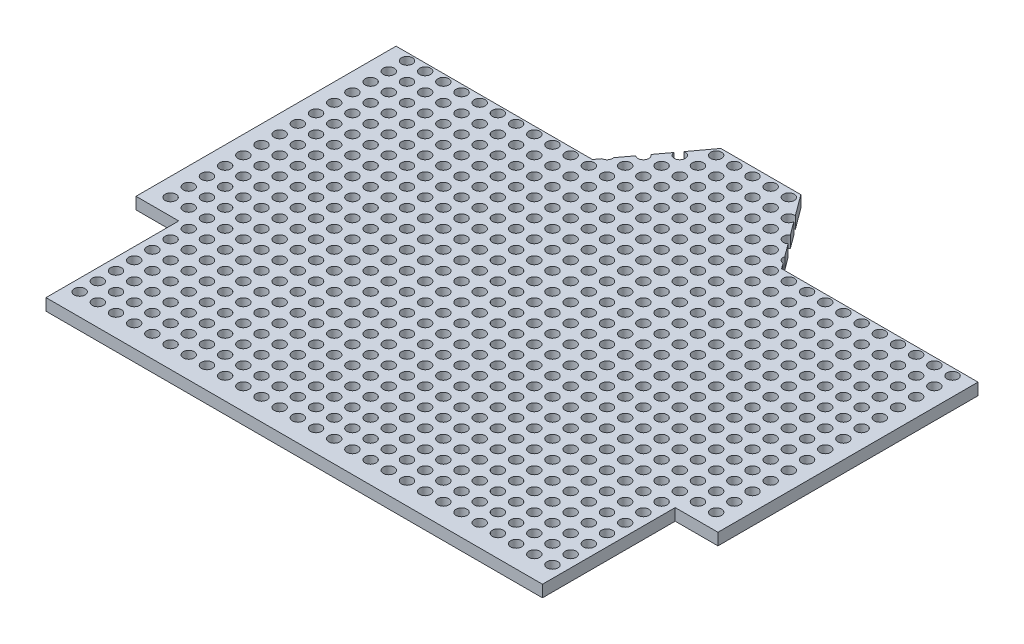
SolidWorks part; units mm, degrees
material "ABS"
ref_plane "Front Plane" through (0, 0, 0) normal (0, 0, 1) x (1, 0, 0)
ref_plane "Top Plane" through (0, 0, 0) normal (0, 1, 0) x (1, 0, 0)
ref_plane "Right Plane" through (0, 0, 0) normal (1, 0, 0) x (0, 0, -1)
sketch "Sketch1" plane through (0, 0, 0) normal (0, 1, 0) x (1, 0, 0)
  line L0 (-80, 35.75) -> (80, -35.75) construction
  line L1 (-11, 56.0362) -> (11, 56.0362)
  line L2 (-80, 35.75) -> (-80, -35.75)
  line L3 (-68.25, -72.25) -> (68.25, -72.25)
  line L4 (80, 35.75) -> (80, -35.75)
  line L5 (-80, -35.75) -> (-68.25, -35.75)
  line L6 (-68.25, -72.25) -> (-68.25, -35.75)
  line L7 (68.25, -72.25) -> (68.25, -35.75)
  line L8 (68.25, -35.75) -> (80, -35.75)
  line L9 (-80, 35.75) -> (-26, 35.75)
  line L10 (-26, 35.75) -> (-11, 56.0362)
  line L11 (11, 56.0362) -> (26, 35.75)
  line L12 (26, 35.75) -> (80, 35.75)
  line L13 (-75, 33.75) -> (-70, 33.75) construction
  line L14 (-75, 28.75) -> (-70, 28.75) construction
  circle A0 centre (-75, 33.75) radius 1.5025
  circle A1 centre (-70, 33.75) radius 1.5025
  circle A2 centre (-65, 33.75) radius 1.5025
  circle A3 centre (-60, 33.75) radius 1.5025
  circle A4 centre (-55, 33.75) radius 1.5025
  circle A5 centre (-50, 33.75) radius 1.5025
  circle A6 centre (-45, 33.75) radius 1.5025
  circle A7 centre (-40, 33.75) radius 1.5025
  circle A8 centre (-35, 33.75) radius 1.5025
  circle A9 centre (-30, 33.75) radius 1.5025
  circle A10 centre (-25, 33.75) radius 1.5025
  circle A11 centre (-20, 33.75) radius 1.5025
  circle A12 centre (-15, 33.75) radius 1.5025
  circle A13 centre (-10, 33.75) radius 1.5025
  circle A14 centre (-5, 33.75) radius 1.5025
  circle A15 centre (0, 33.75) radius 1.5025
  circle A16 centre (5, 33.75) radius 1.5025
  circle A17 centre (10, 33.75) radius 1.5025
  circle A18 centre (15, 33.75) radius 1.5025
  circle A19 centre (20, 33.75) radius 1.5025
  circle A20 centre (25, 33.75) radius 1.5025
  circle A21 centre (30, 33.75) radius 1.5025
  circle A22 centre (35, 33.75) radius 1.5025
  circle A23 centre (40, 33.75) radius 1.5025
  circle A24 centre (45, 33.75) radius 1.5025
  circle A25 centre (50, 33.75) radius 1.5025
  circle A26 centre (55, 33.75) radius 1.5025
  circle A27 centre (60, 33.75) radius 1.5025
  circle A28 centre (65, 33.75) radius 1.5025
  circle A29 centre (70, 33.75) radius 1.5025
  circle A30 centre (75, 33.75) radius 1.5025
  circle A31 centre (-75, 28.75) radius 1.5025
  arc A41 (-24.8897, 37.2516) -> (-23.535, 39.0837) centre (-25, 38.75) ccw
  circle A42 centre (-20, 38.75) radius 1.5025
  circle A43 centre (-15, 38.75) radius 1.5025
  circle A44 centre (-10, 38.75) radius 1.5025
  circle A45 centre (-5, 38.75) radius 1.5025
  circle A46 centre (0, 38.75) radius 1.5025
  circle A47 centre (5, 38.75) radius 1.5025
  circle A48 centre (10, 38.75) radius 1.5025
  circle A49 centre (15, 38.75) radius 1.5025
  circle A50 centre (20, 38.75) radius 1.5025
  arc A51 (23.535, 39.0837) -> (24.8897, 37.2516) centre (25, 38.75) ccw
  arc A72 (-20.9471, 42.5836) -> (-19.1623, 44.9973) centre (-20, 43.75) ccw
  circle A73 centre (-15, 43.75) radius 1.5025
  circle A74 centre (-10, 43.75) radius 1.5025
  circle A75 centre (-5, 43.75) radius 1.5025
  circle A76 centre (0, 43.75) radius 1.5025
  circle A77 centre (5, 43.75) radius 1.5025
  circle A78 centre (10, 43.75) radius 1.5025
  circle A79 centre (15, 43.75) radius 1.5025
  arc A80 (19.1623, 44.9973) -> (20.9471, 42.5836) centre (20, 43.75) ccw
  arc A103 (-16.4954, 48.6041) -> (-15.2987, 50.2225) centre (-15, 48.75) ccw
  circle A104 centre (-10, 48.75) radius 1.5025
  circle A105 centre (-5, 48.75) radius 1.5025
  circle A106 centre (0, 48.75) radius 1.5025
  circle A107 centre (5, 48.75) radius 1.5025
  circle A108 centre (10, 48.75) radius 1.5025
  arc A109 (15.2987, 50.2225) -> (16.4954, 48.6041) centre (15, 48.75) ccw
  circle A134 centre (-10, 53.75) radius 1.5025
  circle A135 centre (-5, 53.75) radius 1.5025
  circle A136 centre (0, 53.75) radius 1.5025
  circle A137 centre (5, 53.75) radius 1.5025
  circle A138 centre (10, 53.75) radius 1.5025
  circle A152 centre (-75, 38.75) radius 1.5025
  circle A156 centre (-70, 28.75) radius 1.5025
  circle A157 centre (-65, 28.75) radius 1.5025
  circle A158 centre (-60, 28.75) radius 1.5025
  circle A159 centre (-55, 28.75) radius 1.5025
  circle A160 centre (-50, 28.75) radius 1.5025
  circle A161 centre (-45, 28.75) radius 1.5025
  circle A162 centre (-40, 28.75) radius 1.5025
  circle A163 centre (-35, 28.75) radius 1.5025
  circle A164 centre (-30, 28.75) radius 1.5025
  circle A165 centre (-25, 28.75) radius 1.5025
  circle A166 centre (-20, 28.75) radius 1.5025
  circle A167 centre (-15, 28.75) radius 1.5025
  circle A168 centre (-10, 28.75) radius 1.5025
  circle A169 centre (-5, 28.75) radius 1.5025
  circle A170 centre (0, 28.75) radius 1.5025
  circle A171 centre (5, 28.75) radius 1.5025
  circle A172 centre (10, 28.75) radius 1.5025
  circle A173 centre (15, 28.75) radius 1.5025
  circle A174 centre (20, 28.75) radius 1.5025
  circle A175 centre (25, 28.75) radius 1.5025
  circle A176 centre (30, 28.75) radius 1.5025
  circle A177 centre (35, 28.75) radius 1.5025
  circle A178 centre (40, 28.75) radius 1.5025
  circle A179 centre (45, 28.75) radius 1.5025
  circle A180 centre (50, 28.75) radius 1.5025
  circle A181 centre (55, 28.75) radius 1.5025
  circle A182 centre (60, 28.75) radius 1.5025
  circle A183 centre (65, 28.75) radius 1.5025
  circle A184 centre (70, 28.75) radius 1.5025
  circle A185 centre (75, 28.75) radius 1.5025
  circle A186 centre (-70, 23.75) radius 1.5025
  circle A187 centre (-65, 23.75) radius 1.5025
  circle A188 centre (-60, 23.75) radius 1.5025
  circle A189 centre (-55, 23.75) radius 1.5025
  circle A190 centre (-50, 23.75) radius 1.5025
  circle A191 centre (-45, 23.75) radius 1.5025
  circle A192 centre (-40, 23.75) radius 1.5025
  circle A193 centre (-35, 23.75) radius 1.5025
  circle A194 centre (-30, 23.75) radius 1.5025
  circle A195 centre (-25, 23.75) radius 1.5025
  circle A196 centre (-20, 23.75) radius 1.5025
  circle A197 centre (-15, 23.75) radius 1.5025
  circle A198 centre (-10, 23.75) radius 1.5025
  circle A199 centre (-5, 23.75) radius 1.5025
  circle A200 centre (0, 23.75) radius 1.5025
  circle A201 centre (5, 23.75) radius 1.5025
  circle A202 centre (10, 23.75) radius 1.5025
  circle A203 centre (15, 23.75) radius 1.5025
  circle A204 centre (20, 23.75) radius 1.5025
  circle A205 centre (25, 23.75) radius 1.5025
  circle A206 centre (30, 23.75) radius 1.5025
  circle A207 centre (35, 23.75) radius 1.5025
  circle A208 centre (40, 23.75) radius 1.5025
  circle A209 centre (45, 23.75) radius 1.5025
  circle A210 centre (50, 23.75) radius 1.5025
  circle A211 centre (55, 23.75) radius 1.5025
  circle A212 centre (60, 23.75) radius 1.5025
  circle A213 centre (65, 23.75) radius 1.5025
  circle A214 centre (70, 23.75) radius 1.5025
  circle A215 centre (75, 23.75) radius 1.5025
  circle A216 centre (-70, 18.75) radius 1.5025
  circle A217 centre (-65, 18.75) radius 1.5025
  circle A218 centre (-60, 18.75) radius 1.5025
  circle A219 centre (-55, 18.75) radius 1.5025
  circle A220 centre (-50, 18.75) radius 1.5025
  circle A221 centre (-45, 18.75) radius 1.5025
  circle A222 centre (-40, 18.75) radius 1.5025
  circle A223 centre (-35, 18.75) radius 1.5025
  circle A224 centre (-30, 18.75) radius 1.5025
  circle A225 centre (-25, 18.75) radius 1.5025
  circle A226 centre (-20, 18.75) radius 1.5025
  circle A227 centre (-15, 18.75) radius 1.5025
  circle A228 centre (-10, 18.75) radius 1.5025
  circle A229 centre (-5, 18.75) radius 1.5025
  circle A230 centre (0, 18.75) radius 1.5025
  circle A231 centre (5, 18.75) radius 1.5025
  circle A232 centre (10, 18.75) radius 1.5025
  circle A233 centre (15, 18.75) radius 1.5025
  circle A234 centre (20, 18.75) radius 1.5025
  circle A235 centre (25, 18.75) radius 1.5025
  circle A236 centre (30, 18.75) radius 1.5025
  circle A237 centre (35, 18.75) radius 1.5025
  circle A238 centre (40, 18.75) radius 1.5025
  circle A239 centre (45, 18.75) radius 1.5025
  circle A240 centre (50, 18.75) radius 1.5025
  circle A241 centre (55, 18.75) radius 1.5025
  circle A242 centre (60, 18.75) radius 1.5025
  circle A243 centre (65, 18.75) radius 1.5025
  circle A244 centre (70, 18.75) radius 1.5025
  circle A245 centre (75, 18.75) radius 1.5025
  circle A246 centre (-70, 13.75) radius 1.5025
  circle A247 centre (-65, 13.75) radius 1.5025
  circle A248 centre (-60, 13.75) radius 1.5025
  circle A249 centre (-55, 13.75) radius 1.5025
  circle A250 centre (-50, 13.75) radius 1.5025
  circle A251 centre (-45, 13.75) radius 1.5025
  circle A252 centre (-40, 13.75) radius 1.5025
  circle A253 centre (-35, 13.75) radius 1.5025
  circle A254 centre (-30, 13.75) radius 1.5025
  circle A255 centre (-25, 13.75) radius 1.5025
  circle A256 centre (-20, 13.75) radius 1.5025
  circle A257 centre (-15, 13.75) radius 1.5025
  circle A258 centre (-10, 13.75) radius 1.5025
  circle A259 centre (-5, 13.75) radius 1.5025
  circle A260 centre (0, 13.75) radius 1.5025
  circle A261 centre (5, 13.75) radius 1.5025
  circle A262 centre (10, 13.75) radius 1.5025
  circle A263 centre (15, 13.75) radius 1.5025
  circle A264 centre (20, 13.75) radius 1.5025
  circle A265 centre (25, 13.75) radius 1.5025
  circle A266 centre (30, 13.75) radius 1.5025
  circle A267 centre (35, 13.75) radius 1.5025
  circle A268 centre (40, 13.75) radius 1.5025
  circle A269 centre (45, 13.75) radius 1.5025
  circle A270 centre (50, 13.75) radius 1.5025
  circle A271 centre (55, 13.75) radius 1.5025
  circle A272 centre (60, 13.75) radius 1.5025
  circle A273 centre (65, 13.75) radius 1.5025
  circle A274 centre (70, 13.75) radius 1.5025
  circle A275 centre (75, 13.75) radius 1.5025
  circle A276 centre (-70, 8.75) radius 1.5025
  circle A277 centre (-65, 8.75) radius 1.5025
  circle A278 centre (-60, 8.75) radius 1.5025
  circle A279 centre (-55, 8.75) radius 1.5025
  circle A280 centre (-50, 8.75) radius 1.5025
  circle A281 centre (-45, 8.75) radius 1.5025
  circle A282 centre (-40, 8.75) radius 1.5025
  circle A283 centre (-35, 8.75) radius 1.5025
  circle A284 centre (-30, 8.75) radius 1.5025
  circle A285 centre (-25, 8.75) radius 1.5025
  circle A286 centre (-20, 8.75) radius 1.5025
  circle A287 centre (-15, 8.75) radius 1.5025
  circle A288 centre (-10, 8.75) radius 1.5025
  circle A289 centre (-5, 8.75) radius 1.5025
  circle A290 centre (0, 8.75) radius 1.5025
  circle A291 centre (5, 8.75) radius 1.5025
  circle A292 centre (10, 8.75) radius 1.5025
  circle A293 centre (15, 8.75) radius 1.5025
  circle A294 centre (20, 8.75) radius 1.5025
  circle A295 centre (25, 8.75) radius 1.5025
  circle A296 centre (30, 8.75) radius 1.5025
  circle A297 centre (35, 8.75) radius 1.5025
  circle A298 centre (40, 8.75) radius 1.5025
  circle A299 centre (45, 8.75) radius 1.5025
  circle A300 centre (50, 8.75) radius 1.5025
  circle A301 centre (55, 8.75) radius 1.5025
  circle A302 centre (60, 8.75) radius 1.5025
  circle A303 centre (65, 8.75) radius 1.5025
  circle A304 centre (70, 8.75) radius 1.5025
  circle A305 centre (75, 8.75) radius 1.5025
  circle A306 centre (-70, 3.75) radius 1.5025
  circle A307 centre (-65, 3.75) radius 1.5025
  circle A308 centre (-60, 3.75) radius 1.5025
  circle A309 centre (-55, 3.75) radius 1.5025
  circle A310 centre (-50, 3.75) radius 1.5025
  circle A311 centre (-45, 3.75) radius 1.5025
  circle A312 centre (-40, 3.75) radius 1.5025
  circle A313 centre (-35, 3.75) radius 1.5025
  circle A314 centre (-30, 3.75) radius 1.5025
  circle A315 centre (-25, 3.75) radius 1.5025
  circle A316 centre (-20, 3.75) radius 1.5025
  circle A317 centre (-15, 3.75) radius 1.5025
  circle A318 centre (-10, 3.75) radius 1.5025
  circle A319 centre (-5, 3.75) radius 1.5025
  circle A320 centre (0, 3.75) radius 1.5025
  circle A321 centre (5, 3.75) radius 1.5025
  circle A322 centre (10, 3.75) radius 1.5025
  circle A323 centre (15, 3.75) radius 1.5025
  circle A324 centre (20, 3.75) radius 1.5025
  circle A325 centre (25, 3.75) radius 1.5025
  circle A326 centre (30, 3.75) radius 1.5025
  circle A327 centre (35, 3.75) radius 1.5025
  circle A328 centre (40, 3.75) radius 1.5025
  circle A329 centre (45, 3.75) radius 1.5025
  circle A330 centre (50, 3.75) radius 1.5025
  circle A331 centre (55, 3.75) radius 1.5025
  circle A332 centre (60, 3.75) radius 1.5025
  circle A333 centre (65, 3.75) radius 1.5025
  circle A334 centre (70, 3.75) radius 1.5025
  circle A335 centre (75, 3.75) radius 1.5025
  circle A336 centre (-70, -1.25) radius 1.5025
  circle A337 centre (-65, -1.25) radius 1.5025
  circle A338 centre (-60, -1.25) radius 1.5025
  circle A339 centre (-55, -1.25) radius 1.5025
  circle A340 centre (-50, -1.25) radius 1.5025
  circle A341 centre (-45, -1.25) radius 1.5025
  circle A342 centre (-40, -1.25) radius 1.5025
  circle A343 centre (-35, -1.25) radius 1.5025
  circle A344 centre (-30, -1.25) radius 1.5025
  circle A345 centre (-25, -1.25) radius 1.5025
  circle A346 centre (-20, -1.25) radius 1.5025
  circle A347 centre (-15, -1.25) radius 1.5025
  circle A348 centre (-10, -1.25) radius 1.5025
  circle A349 centre (-5, -1.25) radius 1.5025
  circle A350 centre (0, -1.25) radius 1.5025
  circle A351 centre (5, -1.25) radius 1.5025
  circle A352 centre (10, -1.25) radius 1.5025
  circle A353 centre (15, -1.25) radius 1.5025
  circle A354 centre (20, -1.25) radius 1.5025
  circle A355 centre (25, -1.25) radius 1.5025
  circle A356 centre (30, -1.25) radius 1.5025
  circle A357 centre (35, -1.25) radius 1.5025
  circle A358 centre (40, -1.25) radius 1.5025
  circle A359 centre (45, -1.25) radius 1.5025
  circle A360 centre (50, -1.25) radius 1.5025
  circle A361 centre (55, -1.25) radius 1.5025
  circle A362 centre (60, -1.25) radius 1.5025
  circle A363 centre (65, -1.25) radius 1.5025
  circle A364 centre (70, -1.25) radius 1.5025
  circle A365 centre (75, -1.25) radius 1.5025
  circle A366 centre (-70, -6.25) radius 1.5025
  circle A367 centre (-65, -6.25) radius 1.5025
  circle A368 centre (-60, -6.25) radius 1.5025
  circle A369 centre (-55, -6.25) radius 1.5025
  circle A370 centre (-50, -6.25) radius 1.5025
  circle A371 centre (-45, -6.25) radius 1.5025
  circle A372 centre (-40, -6.25) radius 1.5025
  circle A373 centre (-35, -6.25) radius 1.5025
  circle A374 centre (-30, -6.25) radius 1.5025
  circle A375 centre (-25, -6.25) radius 1.5025
  circle A376 centre (-20, -6.25) radius 1.5025
  circle A377 centre (-15, -6.25) radius 1.5025
  circle A378 centre (-10, -6.25) radius 1.5025
  circle A379 centre (-5, -6.25) radius 1.5025
  circle A380 centre (0, -6.25) radius 1.5025
  circle A381 centre (5, -6.25) radius 1.5025
  circle A382 centre (10, -6.25) radius 1.5025
  circle A383 centre (15, -6.25) radius 1.5025
  circle A384 centre (20, -6.25) radius 1.5025
  circle A385 centre (25, -6.25) radius 1.5025
  circle A386 centre (30, -6.25) radius 1.5025
  circle A387 centre (35, -6.25) radius 1.5025
  circle A388 centre (40, -6.25) radius 1.5025
  circle A389 centre (45, -6.25) radius 1.5025
  circle A390 centre (50, -6.25) radius 1.5025
  circle A391 centre (55, -6.25) radius 1.5025
  circle A392 centre (60, -6.25) radius 1.5025
  circle A393 centre (65, -6.25) radius 1.5025
  circle A394 centre (70, -6.25) radius 1.5025
  circle A395 centre (75, -6.25) radius 1.5025
  circle A396 centre (-70, -11.25) radius 1.5025
  circle A397 centre (-65, -11.25) radius 1.5025
  circle A398 centre (-60, -11.25) radius 1.5025
  circle A399 centre (-55, -11.25) radius 1.5025
  circle A400 centre (-50, -11.25) radius 1.5025
  circle A401 centre (-45, -11.25) radius 1.5025
  circle A402 centre (-40, -11.25) radius 1.5025
  circle A403 centre (-35, -11.25) radius 1.5025
  circle A404 centre (-30, -11.25) radius 1.5025
  circle A405 centre (-25, -11.25) radius 1.5025
  circle A406 centre (-20, -11.25) radius 1.5025
  circle A407 centre (-15, -11.25) radius 1.5025
  circle A408 centre (-10, -11.25) radius 1.5025
  circle A409 centre (-5, -11.25) radius 1.5025
  circle A410 centre (0, -11.25) radius 1.5025
  circle A411 centre (5, -11.25) radius 1.5025
  circle A412 centre (10, -11.25) radius 1.5025
  circle A413 centre (15, -11.25) radius 1.5025
  circle A414 centre (20, -11.25) radius 1.5025
  circle A415 centre (25, -11.25) radius 1.5025
  circle A416 centre (30, -11.25) radius 1.5025
  circle A417 centre (35, -11.25) radius 1.5025
  circle A418 centre (40, -11.25) radius 1.5025
  circle A419 centre (45, -11.25) radius 1.5025
  circle A420 centre (50, -11.25) radius 1.5025
  circle A421 centre (55, -11.25) radius 1.5025
  circle A422 centre (60, -11.25) radius 1.5025
  circle A423 centre (65, -11.25) radius 1.5025
  circle A424 centre (70, -11.25) radius 1.5025
  circle A425 centre (75, -11.25) radius 1.5025
  circle A426 centre (-70, -16.25) radius 1.5025
  circle A427 centre (-65, -16.25) radius 1.5025
  circle A428 centre (-60, -16.25) radius 1.5025
  circle A429 centre (-55, -16.25) radius 1.5025
  circle A430 centre (-50, -16.25) radius 1.5025
  circle A431 centre (-45, -16.25) radius 1.5025
  circle A432 centre (-40, -16.25) radius 1.5025
  circle A433 centre (-35, -16.25) radius 1.5025
  circle A434 centre (-30, -16.25) radius 1.5025
  circle A435 centre (-25, -16.25) radius 1.5025
  circle A436 centre (-20, -16.25) radius 1.5025
  circle A437 centre (-15, -16.25) radius 1.5025
  circle A438 centre (-10, -16.25) radius 1.5025
  circle A439 centre (-5, -16.25) radius 1.5025
  circle A440 centre (0, -16.25) radius 1.5025
  circle A441 centre (5, -16.25) radius 1.5025
  circle A442 centre (10, -16.25) radius 1.5025
  circle A443 centre (15, -16.25) radius 1.5025
  circle A444 centre (20, -16.25) radius 1.5025
  circle A445 centre (25, -16.25) radius 1.5025
  circle A446 centre (30, -16.25) radius 1.5025
  circle A447 centre (35, -16.25) radius 1.5025
  circle A448 centre (40, -16.25) radius 1.5025
  circle A449 centre (45, -16.25) radius 1.5025
  circle A450 centre (50, -16.25) radius 1.5025
  circle A451 centre (55, -16.25) radius 1.5025
  circle A452 centre (60, -16.25) radius 1.5025
  circle A453 centre (65, -16.25) radius 1.5025
  circle A454 centre (70, -16.25) radius 1.5025
  circle A455 centre (75, -16.25) radius 1.5025
  circle A456 centre (-70, -21.25) radius 1.5025
  circle A457 centre (-65, -21.25) radius 1.5025
  circle A458 centre (-60, -21.25) radius 1.5025
  circle A459 centre (-55, -21.25) radius 1.5025
  circle A460 centre (-50, -21.25) radius 1.5025
  circle A461 centre (-45, -21.25) radius 1.5025
  circle A462 centre (-40, -21.25) radius 1.5025
  circle A463 centre (-35, -21.25) radius 1.5025
  circle A464 centre (-30, -21.25) radius 1.5025
  circle A465 centre (-25, -21.25) radius 1.5025
  circle A466 centre (-20, -21.25) radius 1.5025
  circle A467 centre (-15, -21.25) radius 1.5025
  circle A468 centre (-10, -21.25) radius 1.5025
  circle A469 centre (-5, -21.25) radius 1.5025
  circle A470 centre (0, -21.25) radius 1.5025
  circle A471 centre (5, -21.25) radius 1.5025
  circle A472 centre (10, -21.25) radius 1.5025
  circle A473 centre (15, -21.25) radius 1.5025
  circle A474 centre (20, -21.25) radius 1.5025
  circle A475 centre (25, -21.25) radius 1.5025
  circle A476 centre (30, -21.25) radius 1.5025
  circle A477 centre (35, -21.25) radius 1.5025
  circle A478 centre (40, -21.25) radius 1.5025
  circle A479 centre (45, -21.25) radius 1.5025
  circle A480 centre (50, -21.25) radius 1.5025
  circle A481 centre (55, -21.25) radius 1.5025
  circle A482 centre (60, -21.25) radius 1.5025
  circle A483 centre (65, -21.25) radius 1.5025
  circle A484 centre (70, -21.25) radius 1.5025
  circle A485 centre (75, -21.25) radius 1.5025
  circle A486 centre (-70, -26.25) radius 1.5025
  circle A487 centre (-65, -26.25) radius 1.5025
  circle A488 centre (-60, -26.25) radius 1.5025
  circle A489 centre (-55, -26.25) radius 1.5025
  circle A490 centre (-50, -26.25) radius 1.5025
  circle A491 centre (-45, -26.25) radius 1.5025
  circle A492 centre (-40, -26.25) radius 1.5025
  circle A493 centre (-35, -26.25) radius 1.5025
  circle A494 centre (-30, -26.25) radius 1.5025
  circle A495 centre (-25, -26.25) radius 1.5025
  circle A496 centre (-20, -26.25) radius 1.5025
  circle A497 centre (-15, -26.25) radius 1.5025
  circle A498 centre (-10, -26.25) radius 1.5025
  circle A499 centre (-5, -26.25) radius 1.5025
  circle A500 centre (0, -26.25) radius 1.5025
  circle A501 centre (5, -26.25) radius 1.5025
  circle A502 centre (10, -26.25) radius 1.5025
  circle A503 centre (15, -26.25) radius 1.5025
  circle A504 centre (20, -26.25) radius 1.5025
  circle A505 centre (25, -26.25) radius 1.5025
  circle A506 centre (30, -26.25) radius 1.5025
  circle A507 centre (35, -26.25) radius 1.5025
  circle A508 centre (40, -26.25) radius 1.5025
  circle A509 centre (45, -26.25) radius 1.5025
  circle A510 centre (50, -26.25) radius 1.5025
  circle A511 centre (55, -26.25) radius 1.5025
  circle A512 centre (60, -26.25) radius 1.5025
  circle A513 centre (65, -26.25) radius 1.5025
  circle A514 centre (70, -26.25) radius 1.5025
  circle A515 centre (75, -26.25) radius 1.5025
  circle A516 centre (-70, -31.25) radius 1.5025
  circle A517 centre (-65, -31.25) radius 1.5025
  circle A518 centre (-60, -31.25) radius 1.5025
  circle A519 centre (-55, -31.25) radius 1.5025
  circle A520 centre (-50, -31.25) radius 1.5025
  circle A521 centre (-45, -31.25) radius 1.5025
  circle A522 centre (-40, -31.25) radius 1.5025
  circle A523 centre (-35, -31.25) radius 1.5025
  circle A524 centre (-30, -31.25) radius 1.5025
  circle A525 centre (-25, -31.25) radius 1.5025
  circle A526 centre (-20, -31.25) radius 1.5025
  circle A527 centre (-15, -31.25) radius 1.5025
  circle A528 centre (-10, -31.25) radius 1.5025
  circle A529 centre (-5, -31.25) radius 1.5025
  circle A530 centre (0, -31.25) radius 1.5025
  circle A531 centre (5, -31.25) radius 1.5025
  circle A532 centre (10, -31.25) radius 1.5025
  circle A533 centre (15, -31.25) radius 1.5025
  circle A534 centre (20, -31.25) radius 1.5025
  circle A535 centre (25, -31.25) radius 1.5025
  circle A536 centre (30, -31.25) radius 1.5025
  circle A537 centre (35, -31.25) radius 1.5025
  circle A538 centre (40, -31.25) radius 1.5025
  circle A539 centre (45, -31.25) radius 1.5025
  circle A540 centre (50, -31.25) radius 1.5025
  circle A541 centre (55, -31.25) radius 1.5025
  circle A542 centre (60, -31.25) radius 1.5025
  circle A543 centre (65, -31.25) radius 1.5025
  circle A544 centre (70, -31.25) radius 1.5025
  circle A545 centre (75, -31.25) radius 1.5025
  circle A547 centre (-65, -36.25) radius 1.5025
  circle A548 centre (-60, -36.25) radius 1.5025
  circle A549 centre (-55, -36.25) radius 1.5025
  circle A550 centre (-50, -36.25) radius 1.5025
  circle A551 centre (-45, -36.25) radius 1.5025
  circle A552 centre (-40, -36.25) radius 1.5025
  circle A553 centre (-35, -36.25) radius 1.5025
  circle A554 centre (-30, -36.25) radius 1.5025
  circle A555 centre (-25, -36.25) radius 1.5025
  circle A556 centre (-20, -36.25) radius 1.5025
  circle A557 centre (-15, -36.25) radius 1.5025
  circle A558 centre (-10, -36.25) radius 1.5025
  circle A559 centre (-5, -36.25) radius 1.5025
  circle A560 centre (0, -36.25) radius 1.5025
  circle A561 centre (5, -36.25) radius 1.5025
  circle A562 centre (10, -36.25) radius 1.5025
  circle A563 centre (15, -36.25) radius 1.5025
  circle A564 centre (20, -36.25) radius 1.5025
  circle A565 centre (25, -36.25) radius 1.5025
  circle A566 centre (30, -36.25) radius 1.5025
  circle A567 centre (35, -36.25) radius 1.5025
  circle A568 centre (40, -36.25) radius 1.5025
  circle A569 centre (45, -36.25) radius 1.5025
  circle A570 centre (50, -36.25) radius 1.5025
  circle A571 centre (55, -36.25) radius 1.5025
  circle A572 centre (60, -36.25) radius 1.5025
  circle A573 centre (65, -36.25) radius 1.5025
  circle A577 centre (-65, -41.25) radius 1.5025
  circle A578 centre (-60, -41.25) radius 1.5025
  circle A579 centre (-55, -41.25) radius 1.5025
  circle A580 centre (-50, -41.25) radius 1.5025
  circle A581 centre (-45, -41.25) radius 1.5025
  circle A582 centre (-40, -41.25) radius 1.5025
  circle A583 centre (-35, -41.25) radius 1.5025
  circle A584 centre (-30, -41.25) radius 1.5025
  circle A585 centre (-25, -41.25) radius 1.5025
  circle A586 centre (-20, -41.25) radius 1.5025
  circle A587 centre (-15, -41.25) radius 1.5025
  circle A588 centre (-10, -41.25) radius 1.5025
  circle A589 centre (-5, -41.25) radius 1.5025
  circle A590 centre (0, -41.25) radius 1.5025
  circle A591 centre (5, -41.25) radius 1.5025
  circle A592 centre (10, -41.25) radius 1.5025
  circle A593 centre (15, -41.25) radius 1.5025
  circle A594 centre (20, -41.25) radius 1.5025
  circle A595 centre (25, -41.25) radius 1.5025
  circle A596 centre (30, -41.25) radius 1.5025
  circle A597 centre (35, -41.25) radius 1.5025
  circle A598 centre (40, -41.25) radius 1.5025
  circle A599 centre (45, -41.25) radius 1.5025
  circle A600 centre (50, -41.25) radius 1.5025
  circle A601 centre (55, -41.25) radius 1.5025
  circle A602 centre (60, -41.25) radius 1.5025
  circle A603 centre (65, -41.25) radius 1.5025
  circle A607 centre (-65, -46.25) radius 1.5025
  circle A608 centre (-60, -46.25) radius 1.5025
  circle A609 centre (-55, -46.25) radius 1.5025
  circle A610 centre (-50, -46.25) radius 1.5025
  circle A611 centre (-45, -46.25) radius 1.5025
  circle A612 centre (-40, -46.25) radius 1.5025
  circle A613 centre (-35, -46.25) radius 1.5025
  circle A614 centre (-30, -46.25) radius 1.5025
  circle A615 centre (-25, -46.25) radius 1.5025
  circle A616 centre (-20, -46.25) radius 1.5025
  circle A617 centre (-15, -46.25) radius 1.5025
  circle A618 centre (-10, -46.25) radius 1.5025
  circle A619 centre (-5, -46.25) radius 1.5025
  circle A620 centre (0, -46.25) radius 1.5025
  circle A621 centre (5, -46.25) radius 1.5025
  circle A622 centre (10, -46.25) radius 1.5025
  circle A623 centre (15, -46.25) radius 1.5025
  circle A624 centre (20, -46.25) radius 1.5025
  circle A625 centre (25, -46.25) radius 1.5025
  circle A626 centre (30, -46.25) radius 1.5025
  circle A627 centre (35, -46.25) radius 1.5025
  circle A628 centre (40, -46.25) radius 1.5025
  circle A629 centre (45, -46.25) radius 1.5025
  circle A630 centre (50, -46.25) radius 1.5025
  circle A631 centre (55, -46.25) radius 1.5025
  circle A632 centre (60, -46.25) radius 1.5025
  circle A633 centre (65, -46.25) radius 1.5025
  circle A637 centre (-65, -51.25) radius 1.5025
  circle A638 centre (-60, -51.25) radius 1.5025
  circle A639 centre (-55, -51.25) radius 1.5025
  circle A640 centre (-50, -51.25) radius 1.5025
  circle A641 centre (-45, -51.25) radius 1.5025
  circle A642 centre (-40, -51.25) radius 1.5025
  circle A643 centre (-35, -51.25) radius 1.5025
  circle A644 centre (-30, -51.25) radius 1.5025
  circle A645 centre (-25, -51.25) radius 1.5025
  circle A646 centre (-20, -51.25) radius 1.5025
  circle A647 centre (-15, -51.25) radius 1.5025
  circle A648 centre (-10, -51.25) radius 1.5025
  circle A649 centre (-5, -51.25) radius 1.5025
  circle A650 centre (0, -51.25) radius 1.5025
  circle A651 centre (5, -51.25) radius 1.5025
  circle A652 centre (10, -51.25) radius 1.5025
  circle A653 centre (15, -51.25) radius 1.5025
  circle A654 centre (20, -51.25) radius 1.5025
  circle A655 centre (25, -51.25) radius 1.5025
  circle A656 centre (30, -51.25) radius 1.5025
  circle A657 centre (35, -51.25) radius 1.5025
  circle A658 centre (40, -51.25) radius 1.5025
  circle A659 centre (45, -51.25) radius 1.5025
  circle A660 centre (50, -51.25) radius 1.5025
  circle A661 centre (55, -51.25) radius 1.5025
  circle A662 centre (60, -51.25) radius 1.5025
  circle A663 centre (65, -51.25) radius 1.5025
  circle A667 centre (-65, -56.25) radius 1.5025
  circle A668 centre (-60, -56.25) radius 1.5025
  circle A669 centre (-55, -56.25) radius 1.5025
  circle A670 centre (-50, -56.25) radius 1.5025
  circle A671 centre (-45, -56.25) radius 1.5025
  circle A672 centre (-40, -56.25) radius 1.5025
  circle A673 centre (-35, -56.25) radius 1.5025
  circle A674 centre (-30, -56.25) radius 1.5025
  circle A675 centre (-25, -56.25) radius 1.5025
  circle A676 centre (-20, -56.25) radius 1.5025
  circle A677 centre (-15, -56.25) radius 1.5025
  circle A678 centre (-10, -56.25) radius 1.5025
  circle A679 centre (-5, -56.25) radius 1.5025
  circle A680 centre (0, -56.25) radius 1.5025
  circle A681 centre (5, -56.25) radius 1.5025
  circle A682 centre (10, -56.25) radius 1.5025
  circle A683 centre (15, -56.25) radius 1.5025
  circle A684 centre (20, -56.25) radius 1.5025
  circle A685 centre (25, -56.25) radius 1.5025
  circle A686 centre (30, -56.25) radius 1.5025
  circle A687 centre (35, -56.25) radius 1.5025
  circle A688 centre (40, -56.25) radius 1.5025
  circle A689 centre (45, -56.25) radius 1.5025
  circle A690 centre (50, -56.25) radius 1.5025
  circle A691 centre (55, -56.25) radius 1.5025
  circle A692 centre (60, -56.25) radius 1.5025
  circle A693 centre (65, -56.25) radius 1.5025
  circle A697 centre (-65, -61.25) radius 1.5025
  circle A698 centre (-60, -61.25) radius 1.5025
  circle A699 centre (-55, -61.25) radius 1.5025
  circle A700 centre (-50, -61.25) radius 1.5025
  circle A701 centre (-45, -61.25) radius 1.5025
  circle A702 centre (-40, -61.25) radius 1.5025
  circle A703 centre (-35, -61.25) radius 1.5025
  circle A704 centre (-30, -61.25) radius 1.5025
  circle A705 centre (-25, -61.25) radius 1.5025
  circle A706 centre (-20, -61.25) radius 1.5025
  circle A707 centre (-15, -61.25) radius 1.5025
  circle A708 centre (-10, -61.25) radius 1.5025
  circle A709 centre (-5, -61.25) radius 1.5025
  circle A710 centre (0, -61.25) radius 1.5025
  circle A711 centre (5, -61.25) radius 1.5025
  circle A712 centre (10, -61.25) radius 1.5025
  circle A713 centre (15, -61.25) radius 1.5025
  circle A714 centre (20, -61.25) radius 1.5025
  circle A715 centre (25, -61.25) radius 1.5025
  circle A716 centre (30, -61.25) radius 1.5025
  circle A717 centre (35, -61.25) radius 1.5025
  circle A718 centre (40, -61.25) radius 1.5025
  circle A719 centre (45, -61.25) radius 1.5025
  circle A720 centre (50, -61.25) radius 1.5025
  circle A721 centre (55, -61.25) radius 1.5025
  circle A722 centre (60, -61.25) radius 1.5025
  circle A723 centre (65, -61.25) radius 1.5025
  circle A727 centre (-65, -66.25) radius 1.5025
  circle A728 centre (-60, -66.25) radius 1.5025
  circle A729 centre (-55, -66.25) radius 1.5025
  circle A730 centre (-50, -66.25) radius 1.5025
  circle A731 centre (-45, -66.25) radius 1.5025
  circle A732 centre (-40, -66.25) radius 1.5025
  circle A733 centre (-35, -66.25) radius 1.5025
  circle A734 centre (-30, -66.25) radius 1.5025
  circle A735 centre (-25, -66.25) radius 1.5025
  circle A736 centre (-20, -66.25) radius 1.5025
  circle A737 centre (-15, -66.25) radius 1.5025
  circle A738 centre (-10, -66.25) radius 1.5025
  circle A739 centre (-5, -66.25) radius 1.5025
  circle A740 centre (0, -66.25) radius 1.5025
  circle A741 centre (5, -66.25) radius 1.5025
  circle A742 centre (10, -66.25) radius 1.5025
  circle A743 centre (15, -66.25) radius 1.5025
  circle A744 centre (20, -66.25) radius 1.5025
  circle A745 centre (25, -66.25) radius 1.5025
  circle A746 centre (30, -66.25) radius 1.5025
  circle A747 centre (35, -66.25) radius 1.5025
  circle A748 centre (40, -66.25) radius 1.5025
  circle A749 centre (45, -66.25) radius 1.5025
  circle A750 centre (50, -66.25) radius 1.5025
  circle A751 centre (55, -66.25) radius 1.5025
  circle A752 centre (60, -66.25) radius 1.5025
  circle A753 centre (65, -66.25) radius 1.5025
  circle A756 centre (-75, 23.75) radius 1.5025
  circle A757 centre (-75, 18.75) radius 1.5025
  circle A758 centre (-75, 13.75) radius 1.5025
  circle A759 centre (-75, 8.75) radius 1.5025
  circle A760 centre (-75, 3.75) radius 1.5025
  circle A761 centre (-75, -1.25) radius 1.5025
  circle A762 centre (-75, -6.25) radius 1.5025
  circle A763 centre (-75, -11.25) radius 1.5025
  circle A764 centre (-75, -16.25) radius 1.5025
  circle A765 centre (-75, -21.25) radius 1.5025
  circle A766 centre (-75, -26.25) radius 1.5025
  circle A767 centre (-75, -31.25) radius 1.5025
  circle A775 centre (-75, 53.75) radius 1.5025 [skipped]
  circle A776 centre (-70, 53.75) radius 1.5025 [skipped]
  circle A777 centre (-65, 53.75) radius 1.5025 [skipped]
  circle A778 centre (-55, 53.75) radius 1.5025 [skipped]
  circle A779 centre (-40, 53.75) radius 1.5025 [skipped]
  circle A780 centre (-35, 53.75) radius 1.5025 [skipped]
  circle A781 centre (-30, 53.75) radius 1.5025 [skipped]
  circle A782 centre (-25, 53.75) radius 1.5025 [skipped]
  circle A783 centre (-20, 53.75) radius 1.5025 [skipped]
  circle A784 centre (-45, 53.75) radius 1.5025 [skipped]
  circle A785 centre (-50, 53.75) radius 1.5025 [skipped]
  circle A786 centre (-60, 53.75) radius 1.5025 [skipped]
  circle A787 centre (-60, 48.75) radius 1.5025 [skipped]
  circle A788 centre (-45, 48.75) radius 1.5025 [skipped]
  circle A789 centre (-15, 53.75) radius 1.5025 [skipped]
  circle A790 centre (-20, 48.75) radius 1.5025 [skipped]
  circle A791 centre (-25, 48.75) radius 1.5025 [skipped]
  circle A792 centre (-30, 48.75) radius 1.5025 [skipped]
  circle A793 centre (-35, 48.75) radius 1.5025 [skipped]
  circle A794 centre (-40, 48.75) radius 1.5025 [skipped]
  circle A795 centre (-50, 48.75) radius 1.5025 [skipped]
  circle A796 centre (-65, 48.75) radius 1.5025 [skipped]
  circle A797 centre (-70, 48.75) radius 1.5025 [skipped]
  circle A798 centre (-75, 48.75) radius 1.5025 [skipped]
  circle A799 centre (-75, 43.75) radius 1.5025 [skipped]
  circle A800 centre (-70, 43.75) radius 1.5025 [skipped]
  circle A801 centre (-65, 43.75) radius 1.5025 [skipped]
  circle A802 centre (-60, 43.75) radius 1.5025 [skipped]
  circle A803 centre (-50, 43.75) radius 1.5025 [skipped]
  circle A804 centre (-45, 43.75) radius 1.5025 [skipped]
  circle A805 centre (-40, 43.75) radius 1.5025 [skipped]
  circle A806 centre (-35, 43.75) radius 1.5025 [skipped]
  circle A807 centre (-30, 43.75) radius 1.5025 [skipped]
  circle A808 centre (-25, 43.75) radius 1.5025 [skipped]
  circle A809 centre (-30, 38.75) radius 1.5025 [skipped]
  circle A810 centre (-35, 38.75) radius 1.5025 [skipped]
  circle A811 centre (-40, 38.75) radius 1.5025 [skipped]
  circle A812 centre (-45, 38.75) radius 1.5025 [skipped]
  circle A813 centre (-50, 38.75) radius 1.5025 [skipped]
  circle A814 centre (-55, 38.75) radius 1.5025 [skipped]
  circle A815 centre (-60, 38.75) radius 1.5025 [skipped]
  circle A816 centre (-65, 38.75) radius 1.5025 [skipped]
  circle A817 centre (-70, 38.75) radius 1.5025 [skipped]
  circle A818 centre (-55, 43.75) radius 1.5025 [skipped]
  circle A819 centre (-55, 48.75) radius 1.5025 [skipped]
  circle A820 centre (15, 53.75) radius 1.5025 [skipped]
  circle A821 centre (20, 53.75) radius 1.5025 [skipped]
  circle A822 centre (25, 53.75) radius 1.5025 [skipped]
  circle A823 centre (30, 53.75) radius 1.5025 [skipped]
  circle A824 centre (35, 53.75) radius 1.5025 [skipped]
  circle A825 centre (40, 53.75) radius 1.5025 [skipped]
  circle A826 centre (45, 53.75) radius 1.5025 [skipped]
  circle A827 centre (50, 53.75) radius 1.5025 [skipped]
  circle A828 centre (55, 53.75) radius 1.5025 [skipped]
  circle A829 centre (60, 53.75) radius 1.5025 [skipped]
  circle A830 centre (65, 53.75) radius 1.5025 [skipped]
  circle A831 centre (70, 53.75) radius 1.5025 [skipped]
  circle A832 centre (75, 53.75) radius 1.5025 [skipped]
  circle A833 centre (75, 48.75) radius 1.5025 [skipped]
  circle A834 centre (70, 48.75) radius 1.5025 [skipped]
  circle A835 centre (60, 48.75) radius 1.5025 [skipped]
  circle A836 centre (50, 48.75) radius 1.5025 [skipped]
  circle A837 centre (35, 48.75) radius 1.5025 [skipped]
  circle A838 centre (30, 48.75) radius 1.5025 [skipped]
  circle A839 centre (25, 48.75) radius 1.5025 [skipped]
  circle A840 centre (20, 48.75) radius 1.5025 [skipped]
  circle A841 centre (25, 43.75) radius 1.5025 [skipped]
  circle A842 centre (30, 43.75) radius 1.5025 [skipped]
  circle A843 centre (35, 43.75) radius 1.5025 [skipped]
  circle A844 centre (40, 43.75) radius 1.5025 [skipped]
  circle A845 centre (45, 43.75) radius 1.5025 [skipped]
  circle A846 centre (50, 43.75) radius 1.5025 [skipped]
  circle A847 centre (55, 43.75) radius 1.5025 [skipped]
  circle A848 centre (60, 43.75) radius 1.5025 [skipped]
  circle A849 centre (65, 43.75) radius 1.5025 [skipped]
  circle A850 centre (70, 43.75) radius 1.5025 [skipped]
  circle A851 centre (75, 43.75) radius 1.5025 [skipped]
  circle A852 centre (75, 38.75) radius 1.5025 [skipped]
  circle A853 centre (70, 38.75) radius 1.5025 [skipped]
  circle A854 centre (65, 38.75) radius 1.5025 [skipped]
  circle A855 centre (60, 38.75) radius 1.5025 [skipped]
  circle A856 centre (55, 38.75) radius 1.5025 [skipped]
  circle A857 centre (50, 38.75) radius 1.5025 [skipped]
  circle A858 centre (45, 38.75) radius 1.5025 [skipped]
  circle A859 centre (40, 38.75) radius 1.5025 [skipped]
  circle A860 centre (35, 38.75) radius 1.5025 [skipped]
  circle A861 centre (30, 38.75) radius 1.5025 [skipped]
  circle A862 centre (40, 48.75) radius 1.5025 [skipped]
  circle A863 centre (45, 48.75) radius 1.5025 [skipped]
  circle A864 centre (55, 48.75) radius 1.5025 [skipped]
  circle A865 centre (65, 48.75) radius 1.5025 [skipped]
  circle A866 centre (75, -66.25) radius 1.5025 [skipped]
  circle A867 centre (75, -61.25) radius 1.5025 [skipped]
  circle A868 centre (75, -56.25) radius 1.5025 [skipped]
  circle A869 centre (75, -51.25) radius 1.5025 [skipped]
  circle A870 centre (75, -46.25) radius 1.5025 [skipped]
  circle A871 centre (75, -41.25) radius 1.5025 [skipped]
  arc A872 (76.4169, -35.75) -> (73.5831, -35.75) centre (75, -36.25) ccw [skipped]
  circle A873 centre (70, -41.25) radius 1.5025 [skipped]
  arc A874 (71.4169, -35.75) -> (68.5831, -35.75) centre (70, -36.25) ccw [skipped]
  circle A875 centre (70, -46.25) radius 1.5025 [skipped]
  circle A876 centre (70, -51.25) radius 1.5025 [skipped]
  circle A877 centre (70, -56.25) radius 1.5025 [skipped]
  circle A878 centre (70, -61.25) radius 1.5025 [skipped]
  circle A879 centre (70, -66.25) radius 1.5025 [skipped]
  arc A880 (-76.4169, -35.75) -> (-73.5831, -35.75) centre (-75, -36.25) ccw [skipped]
  arc A881 (-71.4169, -35.75) -> (-68.5831, -35.75) centre (-70, -36.25) ccw [skipped]
  circle A882 centre (-70, -41.25) radius 1.5025 [skipped]
  circle A883 centre (-75, -41.25) radius 1.5025 [skipped]
  circle A884 centre (-75, -46.25) radius 1.5025 [skipped]
  circle A885 centre (-70, -46.25) radius 1.5025 [skipped]
  circle A886 centre (-70, -51.25) radius 1.5025 [skipped]
  circle A887 centre (-75, -51.25) radius 1.5025 [skipped]
  circle A888 centre (-75, -56.25) radius 1.5025 [skipped]
  circle A889 centre (-70, -56.25) radius 1.5025 [skipped]
  circle A890 centre (-70, -61.25) radius 1.5025 [skipped]
  circle A891 centre (-75, -61.25) radius 1.5025 [skipped]
  circle A892 centre (-75, -66.25) radius 1.5025 [skipped]
  circle A893 centre (-70, -66.25) radius 1.5025 [skipped]
  dimension "D12" = 2
  dimension "D13" = 5
  dimension "D14" = 3.005
  dimension "D18" = 5
  dimension "D19" = 5
  dimension "D1" = 108
  dimension "D2" = 52
  dimension "D3" = 22
  dimension "D4" = 71.5
  dimension "D5" = 36.5
  dimension "D6" = 136.5
  dimension "D7" = 15
  dimension "D8" = 160
  dimension "D9" = 54
  dimension "D10" = 11.75
  dimension "D11" = 36.5
  dimension "D17" = 5
  dimension "D22" = 5
  dimension "D15" = 31
  dimension "D16" = 5
  dimension "D20" = 31
  dimension "D21" = 20
extrude "Boss-Extrude1" add sketch "Sketch1" along normal blind 3.25
